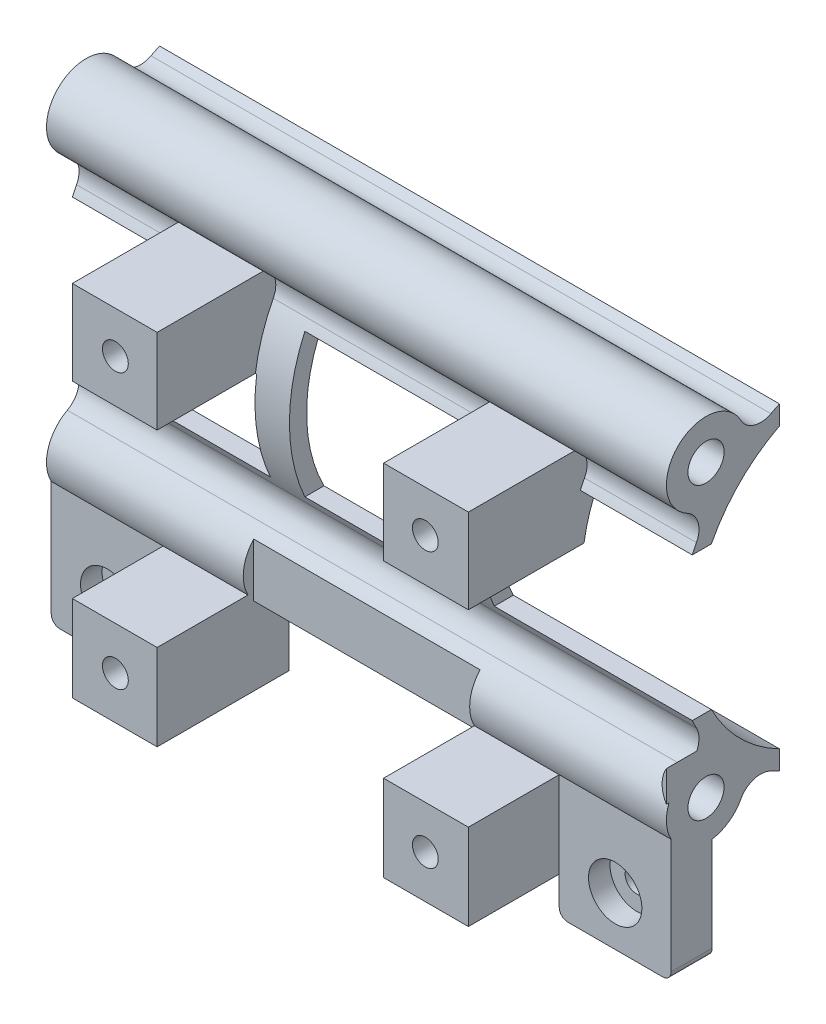
SolidWorks part; units mm, degrees
material "ABS"
ref_plane "Спереди" through (0, 0, 0) normal (0, 0, 1) x (1, 0, 0)
ref_plane "Сверху" through (0, 0, 0) normal (0, 1, 0) x (1, 0, 0)
ref_plane "Справа" through (0, 0, 0) normal (1, 0, 0) x (0, 0, -1)
sketch "Эскиз1" plane through (0, 0, 0) normal (1, 0, 0) x (0, 0, -1)
  circle A0 centre (0, 0) radius 20.25
  dimension "D1" = 40.5
extrude "Бобышка-Вытянуть1" add sketch "Эскиз1" along normal blind 2
sketch "Эскиз2" plane through (0, 0, 0) normal (-1, 0, 0) x (0, 0, 1)
  circle A0 centre (0, 0) radius 3.5
  dimension "D1" = 7
extrude "Вырез-Вытянуть1" cut sketch "Эскиз2" against normal through all
sketch "Эскиз3" plane through (2, 0, 0) normal (1, 0, 0) x (0, 0, -1)
  circle A0 centre (0, 0) radius 10.25
  circle A1 centre (0, 0) radius 20.25
  circle A2 centre (0, 0) radius 20.25 construction
  dimension "D1" = 20.5
extrude "Бобышка-Вытянуть2" add sketch "Эскиз3" along normal blind 4.1
sketch "Эскиз5" plane through (6.1, 0, 0) normal (1, 0, 0) x (0, 0, -1)
  circle A0 centre (0, 0) radius 16.25
  circle A1 centre (0, 0) radius 20.25
  circle A2 centre (0, 0) radius 20.25 construction
  dimension "D2" = 32.5
extrude "Бобышка-Вытянуть3" add sketch "Эскиз5" along normal blind 5.4
sketch "Эскиз6" plane through (11.5, 0, 0) normal (1, 0, 0) x (0, 0, -1)
  circle A0 centre (0, 0) radius 18.25
  circle A1 centre (0, 0) radius 20.25
  circle A2 centre (0, 0) radius 20.25 construction
  dimension "D2" = 36.5
extrude "Бобышка-Вытянуть4" add sketch "Эскиз6" along normal blind 100 and the other way blind 10
sketch "Эскиз7" plane through (0, 0, 0) normal (-1, 0, 0) x (0, 0, 1)
  line L0 (0, 0) -> (-14.3189, -14.3189) construction
  line L1 (-14.3189, -14.3189) -> (14.3189, 14.3189) construction
  line L2 (0, 0) -> (-14.3189, 14.3189) construction
  line L3 (-14.3189, 14.3189) -> (14.3189, -14.3189) construction
  circle A0 centre (0, 0) radius 20.25 construction
  circle A1 centre (-9.1924, 9.1924) radius 1.5
  dimension "D1" = 13
  dimension "D2" = 3
extrude "Вырез-Вытянуть2" cut sketch "Эскиз7" against normal through all
pattern_circular "Круговой массив1" count 4 over 360 about axis through (0, 0, 0) along (-1, 0, 0) of "Вырез-Вытянуть2"
fillet "Скругление1" radius 0.5 5 edges at (6.1, 0, -10.25) (11.5, 0, -16.25) (6.1, 0, -16.25) (11.5, 0, -18.25) (2, 0, -10.25)
sketch "Эскиз9" plane through (0, 0, 0) normal (-1, 0, 0) x (0, 0, 1)
  line L0 (-21.4838, 21.4838) -> (21.4838, -21.4838) construction
  line L1 (21.4838, 21.4838) -> (-21.4838, -21.4838) construction
  line L2 (0, 0) -> (0, 20.25) construction
  circle A0 centre (0, 0) radius 20.25 construction
  circle A1 centre (-16.8645, 16.8645) radius 2.1
  circle A2 centre (-16.8645, 16.8645) radius 4.6
  point P4 (0, 0)
  point P6 (0, 0)
  point P27 (0, 0)
  dimension "D3" = 4.2
  dimension "D4" = 9.2
  dimension "D1" = 45
  dimension "D2" = 45
  dimension "D5" = 23.85
extrude "Бобышка-Вытянуть6" add sketch "Эскиз9" against normal up to surface (111.5 mm away) up to face at (111.5, 0, -20.25)
sketch "Эскиз10" plane through (0, 0, 0) normal (-1, 0, 0) x (0, 0, 1)
  line L0 (-16.8645, 16.8645) -> (-9.1924, 9.1924) construction
  arc A0 (-12.8153, 19.0472) -> (-9.3288, 17.9732) centre (-10.5266, 20.2808) ccw
  arc A1 (-9.3288, 17.9732) -> (-12.3355, 16.0592) centre (0, 0) ccw
  arc A2 (-16.0592, 12.3355) -> (-12.3355, 16.0592) centre (0, 0) ccw construction
  arc A3 (-19.0472, 12.8153) -> (-12.8153, 19.0472) centre (-16.8645, 16.8645) ccw
  circle A4 centre (-16.8645, 16.8645) radius 4.6 construction
  arc A5 (-19.0472, 12.8153) -> (-17.9732, 9.3288) centre (-20.2808, 10.5266) cw
  arc A6 (-16.0592, 12.3355) -> (-17.9732, 9.3288) centre (0, 0) ccw
  arc M15 (-16.0592, 12.3355) -> (-12.3355, 16.0592) centre (0, 0) ccw
  arc M16 (-12.3355, 16.0592) -> (-16.0592, 12.3355) centre (-16.8645, 16.8645) ccw
  dimension "D1" = 2.6
extrude "Бобышка-Вытянуть7" add sketch "Эскиз10" against normal up to surface (111.5 mm away) contours A0 M16 M15 | A5 M16 M15 region at (0, 17.3535, -11.592) region at (0, 11.592, -17.3535) up to face at (111.5, 2.8991, -2.8991)
pattern_circular "Круговой массив3" count 4 over 360 about axis through (2, 0, 0) along (-1, 0, 0) of "Бобышка-Вытянуть7", "Бобышка-Вытянуть6"
sketch "Эскиз11" plane through (111.5, 0, 0) normal (1, 0, 0) x (0, 0, -1)
  line L1 (-32.25, 11.5) -> (-20.25, 11.5)
  line L2 (-32.25, 11.5) -> (-32.25, -23.5)
  line L3 (-32.25, -23.5) -> (-20.25, -23.5)
  line L4 (-20.25, 11.5) -> (-20.25, -23.5)
  arc A0 (-17.9732, 9.3288) -> (-17.9732, -9.3288) centre (0, 0) ccw construction
  point P7 (-20.25, -6)
  dimension "D1" = 12
  dimension "D2" = 35
  dimension "D3" = 6
extrude "Вырез-Вытянуть3" cut sketch "Эскиз11" against normal blind 26 from offset 42.75 offset against normal yes
ref_plane "Плоскость1" through (55.75, 0, 0) normal (-1, 0, 0) x (0, 0, 1)
sketch "Эскиз17" plane through (2, 0, 0) normal (1, 0, 0) x (0, 0, -1)
  circle A0 centre (0, 0) radius 9
  dimension "D1" = 18
extrude "Вырез-Вытянуть5" cut sketch "Эскиз17" against normal through all
ref_plane "Плоскость3" through (68.75, 0, 0) normal (1, 0, 0) x (0, 0, -1)
ref_plane "Плоскость4" through (42.75, 0, 0) normal (-1, 0, 0) x (0, 0, 1)
sketch "Эскиз19" plane through (111.5, 0, 0) normal (1, 0, 0) x (0, 0, -1)
  line L1 (21.4129, 16.1776) -> (21.4129, -16.1776)
  arc A0 (19.0472, 12.8153) -> (17.9732, 9.3288) centre (20.2808, 10.5266) ccw
  arc A1 (17.9732, -9.3288) -> (19.0472, -12.8153) centre (20.2808, -10.5266) ccw
  arc A2 (17.9732, -9.3288) -> (17.9732, 9.3288) centre (0, 0) ccw
  arc A3 (17.9732, -9.3288) -> (17.9732, 9.3288) centre (0, 0) ccw construction
  arc A4 (19.0472, 12.8153) -> (17.9732, 9.3288) centre (20.2808, 10.5266) ccw construction
  arc A5 (17.9732, -9.3288) -> (19.0472, -12.8153) centre (20.2808, -10.5266) ccw construction
  arc A6 (19.0472, 12.8153) -> (21.4129, 16.1776) centre (16.8645, 16.8645) ccw
  arc A7 (19.0472, 12.8153) -> (12.8153, 19.0472) centre (16.8645, 16.8645) ccw construction
  arc A8 (21.4129, -16.1776) -> (19.0472, -12.8153) centre (16.8645, -16.8645) ccw
  arc A9 (12.8153, -19.0472) -> (19.0472, -12.8153) centre (16.8645, -16.8645) ccw construction
  arc M8 (12.8153, -19.0472) -> (19.0472, -12.8153) centre (16.8645, -16.8645) ccw
  arc M9 (19.0472, -12.8153) -> (17.9732, -9.3288) centre (20.2808, -10.5266) cw
  arc M10 (17.9732, -9.3288) -> (17.9732, 9.3288) centre (0, 0) ccw
  arc M11 (17.9732, 9.3288) -> (19.0472, 12.8153) centre (20.2808, 10.5266) cw
  arc M12 (19.0472, 12.8153) -> (12.8153, 19.0472) centre (16.8645, 16.8645) ccw
extrude "Бобышка-Вытянуть14" add sketch "Эскиз19" against normal up to surface (68.75 mm away) from surface contours L1 M12 M11 M10 | L1 M10 M9 M8 region at (111.5, 0, -21.0872) up to plane "Плоскость4" starting at plane "Плоскость3"
ref_plane "Плоскость8" through (0, 0, 21.4645) normal (0, 0, 1) x (1, 0, 0)
sketch "Эскиз21" plane through (0, 0, 21.4645) normal (0, 0, 1) x (1, 0, 0)
  line L1 (42.75, 8.3288) -> (15, 8.3288)
  line L2 (42.75, 8.3288) -> (42.75, -8.3288)
  line L3 (42.75, -8.3288) -> (15, -8.3288)
  line L4 (15, 8.3288) -> (15, -8.3288)
  line L5 (55.75, 21.4645) -> (55.75, -21.4645) construction
  line L6 (15, 8.3288) -> (15, 9.3288) construction
  line L7 (111.5, 9.3288) -> (0, 9.3288) construction
  line L8 (15, -8.3288) -> (15, -9.3288) construction
  line L9 (111.5, -9.3288) -> (0, -9.3288) construction
  line L10 (111.5, 21.4645) -> (0, 21.4645) construction
  line L14 (0, 9.3288) -> (0, -9.3288) construction
  line L15 (0, -21.4645) -> (111.5, -21.4645) construction
  line L17 (96.5, -8.3288) -> (96.5, -9.3288) construction
  line L18 (96.5, 8.3288) -> (96.5, 9.3288) construction
  line L19 (96.5, 8.3288) -> (96.5, -8.3288)
  line L20 (68.75, -8.3288) -> (96.5, -8.3288)
  line L21 (68.75, 8.3288) -> (68.75, -8.3288)
  line L22 (68.75, 8.3288) -> (96.5, 8.3288)
  dimension "D1" = 1
  dimension "D4" = 15
  dimension "D5" = 42.75
extrude "Вырез-Вытянуть6" cut sketch "Эскиз21" against normal through all
ref_plane "Плоскость5" through (0, 21.4645, 0) normal (0, 1, 0) x (1, 0, 0)
sketch "Эскиз22" plane through (0, 21.4645, 0) normal (0, 1, 0) x (1, 0, 0)
  line L0 (0, 9.3288) -> (0, -9.3288) construction
  line L1 (15, 8.3288) -> (96.5, 8.3288)
  line L2 (15, 8.3288) -> (15, -8.3288)
  line L3 (15, -8.3288) -> (96.5, -8.3288)
  line L4 (96.5, 8.3288) -> (96.5, -8.3288)
  line L5 (111.5, -9.3288) -> (111.5, 9.3288) construction
  line L6 (111.5, 9.3288) -> (0, 9.3288) construction
  line L7 (111.5, -9.3288) -> (0, -9.3288) construction
  dimension "D1" = 15
  dimension "D2" = 15
  dimension "D3" = 1
  dimension "D4" = 1
extrude "Вырез-Вытянуть7" cut sketch "Эскиз22" against normal through all
sketch "Эскиз23" plane through (0, 0, -21.4129) normal (0, 0, -1) x (-1, 0, 0)
  line L0 (-78.75, -21.4645) -> (-55.75, -21.4645) construction
  line L1 (-91.75, -19.3785) -> (-78.75, -19.3785)
  line L2 (-91.75, -19.3785) -> (-91.75, -33.3785)
  line L3 (-91.75, -33.3785) -> (-78.75, -33.3785)
  line L4 (-78.75, -19.3785) -> (-78.75, -33.3785)
  line L5 (-32.75, -19.3785) -> (-19.75, -19.3785)
  line L6 (-32.75, -19.3785) -> (-32.75, -33.3785)
  line L7 (-32.75, -33.3785) -> (-19.75, -33.3785)
  line L8 (-19.75, -19.3785) -> (-19.75, -33.3785)
  line L9 (-55.75, -21.4645) -> (-32.75, -21.4645) construction
  line L10 (-111.5, -12.8153) -> (-111.5, -21.4645) construction
  line L11 (-55.75, 21.4645) -> (-55.75, -21.4645) construction
  line L12 (0, 21.4645) -> (-111.5, 21.4645) construction
  line L13 (-111.5, -21.4645) -> (0, -21.4645) construction
  dimension "D3" = 14
  dimension "D4" = 13
  dimension "D5" = 19.75
extrude "Бобышка-Вытянуть16" add sketch "Эскиз23" against normal blind 2.26 from offset 3 offset against normal yes
sketch "Эскиз24" plane through (0, 0, -18.4129) normal (0, 0, -1) x (-1, 0, 0)
  line L0 (-78.75, -21.1961) -> (-91.75, -21.1961) construction
  line L2 (-32.75, -33.3785) -> (-19.75, -33.3785) construction
  line L4 (-91.75, -33.3785) -> (-78.75, -33.3785) construction
  circle A0 centre (-85.25, -27.6961) radius 1.35
  circle A1 centre (-26.25, -27.6961) radius 1.35
  point P14 (-85.25, -33.3785)
  point P15 (-26.25, -33.3785)
  dimension "D1" = 2.7
  dimension "D2" = 2.7
  dimension "D4" = 6.5
extrude "Вырез-Вытянуть8" cut sketch "Эскиз24" against normal through all
sketch "Эскиз28" plane through (0, 0, -18.4129) normal (0, 0, -1) x (-1, 0, 0)
  line L0 (-78.75, -33.3785) -> (-78.75, -21.1961) construction
  line L1 (-91.75, -33.3785) -> (-78.75, -33.3785)
  line L2 (-91.75, -33.3785) -> (-91.75, -18.3785)
  line L3 (-91.75, -18.3785) -> (-78.75, -18.3785)
  line L4 (-78.75, -33.3785) -> (-78.75, -18.3785)
  line L5 (-19.75, -33.3785) -> (-19.75, -21.1961) construction
  line L6 (-32.75, -33.3785) -> (-19.75, -33.3785)
  line L7 (-32.75, -33.3785) -> (-32.75, -18.3785)
  line L8 (-32.75, -18.3785) -> (-19.75, -18.3785)
  line L9 (-19.75, -33.3785) -> (-19.75, -18.3785)
  circle A0 centre (-85.25, -27.6961) radius 3.1
  circle A1 centre (-26.25, -27.6961) radius 3.1
  dimension "D1" = 6.2
  dimension "D2" = 15
  dimension "D3" = 15
extrude "Бобышка-Вытянуть17" add sketch "Эскиз28" along normal blind 2.5
mirror "Зеркальное отражение1" about plane through (0, 0, 0) normal (0, 0, 1) of "Вырез-Вытянуть8", "Бобышка-Вытянуть16", "Бобышка-Вытянуть17"
fillet "Скругление4" radius 1 8 edges at (19.75, -33.3785, -18.5329) (19.75, -33.3785, 18.5329) (32.75, -33.3785, 18.5329) (32.75, -33.3785, -18.5329) (78.75, -33.3785, -18.5329) (78.75, -33.3785, 18.5329) (91.75, -33.3785, 18.5329) (91.75, -33.3785, -18.5329)
ref_plane "Плоскость7" through (0, -21.4645, 0) normal (0, -1, 0) x (-1, 0, 0)
sketch "Эскиз34" plane through (0, -21.4645, 0) normal (0, -1, 0) x (-1, 0, 0)
  line L0 (-96.5, -8.3288) -> (-96.5, 8.3288) construction
  line L1 (-111.5, 8.3288) -> (-96.5, 8.3288)
  line L2 (-111.5, 8.3288) -> (-111.5, -8.3288)
  line L3 (-111.5, -8.3288) -> (-96.5, -8.3288)
  line L4 (-96.5, 8.3288) -> (-96.5, -8.3288)
  line L5 (-111.5, 9.3288) -> (-111.5, -9.3288) construction
  line L6 (-96.5, 8.3288) -> (-15, 8.3288) construction
  line L7 (-15, -8.3288) -> (-96.5, -8.3288) construction
extrude "Вырез-Вытянуть15" cut sketch "Эскиз34" against normal up to surface (5.2259 mm away) up to face at (55.75, -17.2443, 0)
sketch "Эскиз35" plane through (0, 0, 21.4645) normal (0, 0, 1) x (1, 0, 0)
  line L0 (111.5, 12.8153) -> (0, 12.8153) construction
  line L1 (42.75, 12.8153) -> (32.75, 12.8153)
  line L2 (42.75, 12.8153) -> (42.75, 2.8153)
  line L3 (42.75, 2.8153) -> (32.75, 2.8153)
  line L4 (32.75, 12.8153) -> (32.75, 2.8153)
  line L5 (68.75, -8.3288) -> (68.75, 8.3288) construction
  line L6 (42.75, 8.3288) -> (42.75, -8.3288) construction
  line L11 (68.75, 12.8153) -> (78.75, 12.8153)
  line L12 (68.75, 12.8153) -> (68.75, 2.8153)
  line L13 (68.75, 2.8153) -> (78.75, 2.8153)
  line L14 (78.75, 12.8153) -> (78.75, 2.8153)
  dimension "D1" = 10
  dimension "D2" = 10
extrude "Бобышка-Вытянуть18" add sketch "Эскиз35" against normal up to surface and the other way blind 10 up to face at (63.25, -8.1193, 0)
sketch "Эскиз36" plane through (0, 0, 21.4645) normal (0, 0, 1) x (1, 0, 0)
  line L0 (42.75, 2.8153) -> (42.75, -8.3288) construction
  line L1 (32.75, -19.0486) -> (42.75, -19.0486)
  line L2 (32.75, -19.0486) -> (32.75, -29.0486)
  line L3 (32.75, -29.0486) -> (42.75, -29.0486)
  line L4 (42.75, -19.0486) -> (42.75, -29.0486)
  line L5 (68.75, -19.0486) -> (78.75, -19.0486)
  line L6 (68.75, -19.0486) -> (68.75, -29.0486)
  line L7 (68.75, -29.0486) -> (78.75, -29.0486)
  line L8 (78.75, -19.0486) -> (78.75, -29.0486)
  line L9 (68.75, -8.3288) -> (68.75, 2.8153) construction
  line L10 (19.75, -19.0486) -> (32.75, -19.0486) construction
  dimension "D1" = 10
  dimension "D2" = 10
extrude "Бобышка-Вытянуть19" add sketch "Эскиз36" against normal up to surface and the other way up to surface up to face at (26.25, -29.0461, 16.1529) other way up to face at (37.75, 7.8153, 31.4645)
sketch "Эскиз37" plane through (0, 0, 31.4645) normal (0, 0, 1) x (1, 0, 0)
  line L0 (42.75, 12.8153) -> (32.75, 2.8153) construction
  line L1 (78.75, 12.8153) -> (68.75, 2.8153) construction
  line L2 (42.75, -19.0486) -> (32.75, -29.0486) construction
  line L3 (78.75, -19.0486) -> (68.75, -29.0486) construction
  circle A0 centre (37.75, 7.8153) radius 1.5
  circle A1 centre (73.75, 7.8153) radius 1.5
  circle A2 centre (37.75, -24.0486) radius 1.5
  circle A3 centre (73.75, -24.0486) radius 1.5
  dimension "D1" = 3
extrude "Вырез-Вытянуть16" cut sketch "Эскиз37" against normal blind 20
sketch "Эскиз39" plane through (0, 0, 16.1529) normal (0, 0, -1) x (-1, 0, 0)
  line L1 (-70.7, -24.0486) -> (-72.225, -21.4072)
  line L2 (-72.225, -21.4072) -> (-75.275, -21.4072)
  line L3 (-75.275, -21.4072) -> (-76.8, -24.0486)
  line L4 (-76.8, -24.0486) -> (-75.275, -26.69)
  line L5 (-75.275, -26.69) -> (-72.225, -26.69)
  line L6 (-72.225, -26.69) -> (-70.7, -24.0486)
  line L7 (-34.7, -24.0486) -> (-36.225, -21.4072)
  line L8 (-36.225, -21.4072) -> (-39.275, -21.4072)
  line L9 (-39.275, -21.4072) -> (-40.8, -24.0486)
  line L10 (-40.8, -24.0486) -> (-39.275, -26.69)
  line L11 (-39.275, -26.69) -> (-36.225, -26.69)
  line L12 (-36.225, -26.69) -> (-34.7, -24.0486)
  line L14 (-78.75, -29.0486) -> (-68.75, -29.0486) construction
  line L17 (-42.75, -29.0486) -> (-32.75, -29.0486) construction
  circle A0 centre (-73.75, -24.0486) radius 3.05 construction
  circle A1 centre (-37.75, -24.0486) radius 3.05 construction
  dimension "D1" = 6.1
extrude "Вырез-Вытянуть17" cut sketch "Эскиз39" against normal blind 5
ref_plane "Плоскость9" through (0, 0, 15.4645) normal (0, 0, 1) x (1, 0, 0)
sketch "Эскиз40" plane through (0, 0, 15.4645) normal (0, 0, 1) x (1, 0, 0)
  line L1 (70.7, 7.8153) -> (72.225, 5.1739)
  line L2 (72.225, 5.1739) -> (75.275, 5.1739)
  line L3 (75.275, 5.1739) -> (76.8, 7.8153)
  line L4 (76.8, 7.8153) -> (75.275, 10.4567)
  line L5 (75.275, 10.4567) -> (72.225, 10.4567)
  line L6 (72.225, 10.4567) -> (70.7, 7.8153)
  line L7 (34.7, 7.8153) -> (36.225, 5.1739)
  line L8 (36.225, 5.1739) -> (39.275, 5.1739)
  line L9 (39.275, 5.1739) -> (40.8, 7.8153)
  line L10 (40.8, 7.8153) -> (39.275, 10.4567)
  line L11 (39.275, 10.4567) -> (36.225, 10.4567)
  line L12 (36.225, 10.4567) -> (34.7, 7.8153)
  circle A0 centre (73.75, 7.8153) radius 3.05 construction
  circle A1 centre (37.75, 7.8153) radius 3.05 construction
  dimension "D1" = 6.1
extrude "Вырез-Вытянуть18" cut sketch "Эскиз40" along normal blind 7
sketch "Эскиз41" plane through (0, 12.8153, 0) normal (0, 1, 0) x (1, 0, 0)
  line L1 (32.75, -31.4645) -> (78.75, -31.4645)
  line L2 (32.75, -31.4645) -> (32.75, -19.0472)
  line L3 (32.75, -19.0472) -> (78.75, -19.0472)
  line L4 (78.75, -31.4645) -> (78.75, -19.0472)
  line L6 (68.75, -19.0472) -> (78.75, -19.0472) construction
  line L7 (78.75, -31.4645) -> (78.75, -19.0472) construction
extrude "Вырез-Вытянуть19" cut sketch "Эскиз41" against normal blind 0.17
sketch "Эскиз42" plane through (42.75, 0, 0) normal (1, 0, 0) x (0, 0, -1)
  line L0 (-16.1529, -21.4091) -> (-16.1529, -29.0486)
  line L1 (-16.1529, -29.0486) -> (-31.4645, -29.0486)
  line L2 (-31.4645, -29.0486) -> (-31.4645, -19.0486)
  line L3 (-31.4645, -19.0486) -> (-20.9129, -19.0486)
  line L4 (-20.25, -13.7503) -> (-20.25, -19.9787)
  line L5 (-20.25, -19.9787) -> (-20.25, -13.7503) construction
  line L6 (-19.0472, 12.8153) -> (-19.0472, 12.6453)
  line L7 (-19.0472, 12.6453) -> (-31.4645, 12.6453)
  line L8 (-31.4645, 12.6453) -> (-31.4645, 2.8153)
  line L9 (-31.4645, 2.8153) -> (-20.0533, 2.8153)
  arc A0 (-20.25, -13.7503) -> (-20.9129, -19.0486) centre (-16.8645, -16.8645) ccw
  arc A1 (-20.25, -19.9787) -> (-16.1529, -21.4091) centre (-16.8645, -16.8645) ccw
  arc A2 (-17.9732, 9.3288) -> (-19.0472, 12.8153) centre (-20.2808, 10.5266) ccw
  arc A3 (-17.9732, 9.3288) -> (-19.0472, 12.8153) centre (-20.2808, 10.5266) ccw construction
  arc A4 (-17.9732, 9.3288) -> (-20.0533, 2.8153) centre (0, 0) ccw
  arc A5 (-17.9732, 9.3288) -> (-20.0533, 2.8153) centre (0, 0) ccw construction
  arc M8 (-20.25, -13.7503) -> (-20.9129, -19.0486) centre (-16.8645, -16.8645) ccw
  line M9 (-20.9129, -19.0486) -> (-31.4645, -19.0486)
  line M10 (-31.4645, -19.0486) -> (-31.4645, -29.0486)
  line M11 (-31.4645, -29.0486) -> (-16.1529, -29.0486)
  line M12 (-16.1529, -29.0486) -> (-16.1529, -21.4091)
  arc M13 (-16.1529, -21.4091) -> (-20.25, -19.9787) centre (-16.8645, -16.8645) cw
  line M14 (-20.25, -19.9787) -> (-20.25, -13.7503)
extrude "Вырез-Вытянуть20" cut sketch "Эскиз42" against normal blind 0.15 contours A4 A2 L6 L7 L8 L9 | M14 M8 M9 M10 M11 M12 M13 region at (42.75, -24.0291, 24.0346) region at (42.75, 7.8967, 25.0962)
mirror "Зеркальное отражение2" about plane through (55.75, 0, 0) normal (-1, 0, 0) of "Вырез-Вытянуть20"
sketch "Эскиз43" plane through (0, 0, 21.4645) normal (0, 0, 1) x (1, 0, 0)
  line L0 (111.5, -21.4645) -> (111.5, -12.8153) construction
  line L1 (91.75, -21.4645) -> (111.5, -21.4645) construction
  circle A0 centre (94.75, -13.4545) radius 3.5
  circle A1 centre (94.75, -13.4545) radius 1.35
  dimension "D1" = 7
  dimension "D2" = 2.7
  dimension "D3" = 16.75
  dimension "D4" = 8.01
extrude "Бобышка-Вытянуть20" add sketch "Эскиз43" against normal up to next
sketch "Эскиз44" plane through (0, 0, 21.4645) normal (0, 0, 1) x (1, 0, 0)
  circle A0 centre (94.75, -13.4545) radius 1.35
extrude "Вырез-Вытянуть21" cut sketch "Эскиз44" against normal up to surface (9.1341 mm away) up to face at (73.75, 7.5716, 16.5121)
sketch "Эскиз48" plane through (0, 0, 21.4645) normal (0, 0, 1) x (1, 0, 0)
  line L0 (15, 8.3288) -> (32.75, 8.3288) construction
  line L1 (46.75, 8.3288) -> (64.75, 8.3288)
  line L2 (46.75, 8.3288) -> (46.75, -8.3288)
  line L3 (46.75, -8.3288) -> (64.75, -8.3288)
  line L4 (64.75, 8.3288) -> (64.75, -8.3288)
  line L5 (42.75, -8.3288) -> (15, -8.3288) construction
  line L8 (42.75, -8.3288) -> (46.75, -8.3288) construction
  line L9 (64.75, -8.3288) -> (68.75, -8.3288) construction
  dimension "D1" = 4
extrude "Вырез-Вытянуть26" cut sketch "Эскиз48" against normal up to surface (5.2259 mm away) up to face at (93.4, -13.4484, 12.337)
ref_axis "Ось1" through (12, 0, 0) along (1, 0, 0)
ref_point "ТочкаЦентр"
sketch "Эскиз49" [suppressed] plane through (0, 0, -29.3129) normal (0, 0, -1) x (-1, 0, 0)
  circle A0 centre (-55.75, 2.4276) radius 1.35
  dimension "D1" = 2.7
extrude "Вырез-Вытянуть27" [suppressed] cut sketch "Эскиз49" against normal blind 20
sketch "Эскиз50" plane through (0, 0, -21.4129) normal (0, 0, -1) x (-1, 0, 0)
  line L0 (-42.75, 16.1776) -> (-68.75, 16.1776) construction
  circle A0 centre (-55.75, 2.4276) radius 2.5
  dimension "D2" = 5
  dimension "D1" = 13.75
extrude "Вырез-Вытянуть28" cut sketch "Эскиз50" against normal blind 20
sketch "Эскиз51" plane through (0, 0, -21.4129) normal (0, 0, -1) x (-1, 0, 0)
  circle A0 centre (-55.75, 2.4276) radius 10
  circle A1 centre (-55.75, 2.4276) radius 2.5
  circle A2 centre (-55.75, 2.4276) radius 2.5 construction
  dimension "D1" = 20
extrude "Бобышка-Вытянуть21" add sketch "Эскиз51" along normal blind 5
fillet "Скругление5" radius 3 1 edges at (55.75, -7.5724, -21.4129)
sketch "Эскиз52" plane through (91.75, 0, 0) normal (1, 0, 0) x (0, 0, -1)
  line L1 (-48.2391, 60.1135) -> (48.2391, 60.1135)
  line L2 (-48.2391, 60.1135) -> (-48.2391, -60.1135)
  line L3 (-48.2391, -60.1135) -> (48.2391, -60.1135)
  line L4 (48.2391, 60.1135) -> (48.2391, -60.1135)
  line L5 (-48.2391, 60.1135) -> (48.2391, -60.1135) construction
  line L6 (-48.2391, -60.1135) -> (48.2391, 60.1135) construction
  point P0 (0, 0)
extrude "Вырез-Вытянуть29" cut sketch "Эскиз52" along normal through all
sketch "Эскиз53" plane through (0, 0, 0) normal (-1, 0, 0) x (0, 0, 1)
  line L1 (-57.4481, 61.4264) -> (57.4481, 61.4264)
  line L2 (-57.4481, 61.4264) -> (-57.4481, -61.4264)
  line L3 (-57.4481, -61.4264) -> (57.4481, -61.4264)
  line L4 (57.4481, 61.4264) -> (57.4481, -61.4264)
  line L5 (-57.4481, 61.4264) -> (57.4481, -61.4264) construction
  line L6 (-57.4481, -61.4264) -> (57.4481, 61.4264) construction
  point P0 (0, 0)
extrude "Вырез-Вытянуть30" cut sketch "Эскиз53" against normal up to surface (19.75 mm away) up to face at (19.75, -26.4928, -18.6267)
sketch "Эскиз54" plane through (19.75, 0, 0) normal (-1, 0, 0) x (0, 0, 1)
  circle A0 centre (0, 0) radius 28.45
  arc A3 (-12.8153, 19.0472) -> (-19.0472, 12.8153) centre (-16.8645, 16.8645) ccw construction
extrude "!!!-Для печати" [suppressed] add sketch "Эскиз54" along normal blind 1
sketch "Эскиз55" plane through (91.75, 0, 0) normal (1, 0, 0) x (0, 0, -1)
  line L1 (0, 30.473) -> (60.7544, 30.473)
  line L2 (0, 30.473) -> (0, -52.7762)
  line L3 (0, -52.7762) -> (60.7544, -52.7762)
  line L4 (60.7544, 30.473) -> (60.7544, -52.7762)
extrude "Вырез-Вытянуть31" cut sketch "Эскиз55" against normal through all
